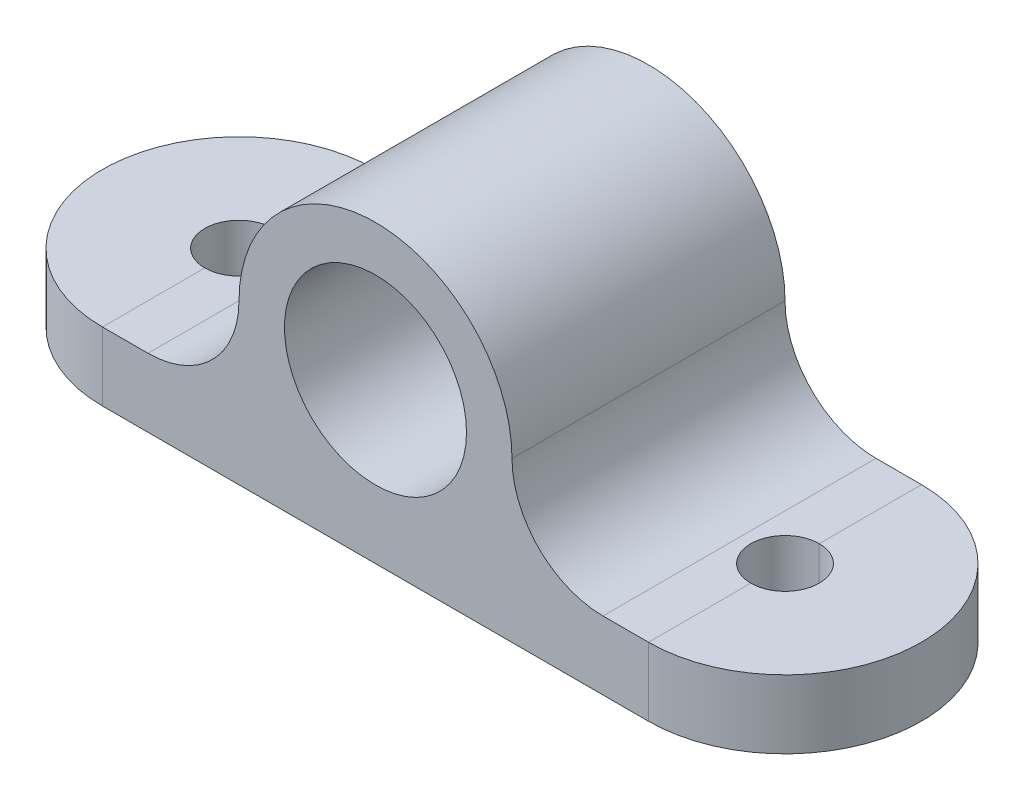
SolidWorks part; units mm, degrees
material "Plain Carbon Steel"
ref_plane "Front Plane" through (0, 0, 0) normal (0, 0, 1) x (1, 0, 0)
ref_plane "Top Plane" through (0, 0, 0) normal (0, 1, 0) x (1, 0, 0)
ref_plane "Right Plane" through (0, 0, 0) normal (1, 0, 0) x (0, 0, -1)
sketch "Sketch1" plane through (0, 0, 0) normal (0, 0, 1) x (1, 0, 0)
  line L0 (28.575, 11.0998) -> (28.575, 4.7752)
  line L1 (0, 0) -> (38.1, 0)
  line L2 (0, 0) -> (0, 4.7752)
  line L3 (0, 4.7752) -> (38.1, 4.7752)
  line L4 (38.1, 0) -> (38.1, 4.7752)
  line L9 (9.525, 4.7752) -> (9.525, 11.0998)
  line L10 (9.525, 4.7752) -> (28.575, 4.7752)
  circle A0 centre (19.05, 11.0998) radius 6.35
  arc A1 (28.575, 11.0998) -> (9.525, 11.0998) centre (19.05, 11.0998) ccw
  point P6 (0, 0)
  dimension "D6" = 12.7
  dimension "D3" = 9.525
  dimension "D4" = 19.05
  dimension "D1" = 38.1
  dimension "D2" = 4.7752
  dimension "D7" = 11.0998
extrude "Boss-Extrude1" add sketch "Sketch1" along normal blind 19.05 contours L0 A1 L9 L3 A0 | A0 L3 L2 L1 L4 | L10 A0 region at (28.3272, 7.9375, 0) region at (19.05, 2.3873, 0) region at (19.05, 11.1008, 0)
extrude "Cut-Extrude1" cut sketch "Sketch1<3>" along normal blind 22.5044 contours A0
sketch "Sketch1<3>" plane through (0, 0, 0) normal (0, 0, 1) x (1, 0, 0) same geometry as "Sketch1"
sketch "Sketch2" plane through (0, 4.7752, 0) normal (0, 1, 0) x (1, 0, 0)
  line L0 (38.1, -19.05) -> (38.1, 0) construction
  line L1 (38.1, 0) -> (38.1, -19.05)
  line L2 (0, -19.05) -> (0, 0) construction
  line L3 (0, -19.05) -> (9.525, -19.05) construction
  line L4 (0, 0) -> (0, -19.05)
  arc A0 (38.1, -19.05) -> (38.1, 0) centre (38.1, -9.525) ccw
  arc A1 (0, 0) -> (0, -19.05) centre (0, -9.525) ccw
extrude "Boss-Extrude2" add sketch "Sketch2" against normal blind 4.7752 separate body
sketch "Sketch3" plane through (0, 4.7752, 0) normal (0, 1, 0) x (1, 0, 0)
  line L0 (38.1, -19.05) -> (38.1, 0) construction
  line L1 (0, -19.05) -> (0, 0) construction
  circle A0 centre (38.1, -9.525) radius 2.3876
  circle A1 centre (0, -9.525) radius 2.3876
  dimension "D1" = 4.7752
  dimension "D2" = 4.7752
extrude "Cut-Extrude2" cut sketch "Sketch3" against normal through all
fillet "Fillet1" radius 6.35 1 edges at (28.575, 4.7752, 9.525)
fillet "Fillet2" radius 6.35 1 edges at (9.525, 4.7752, 9.525)
